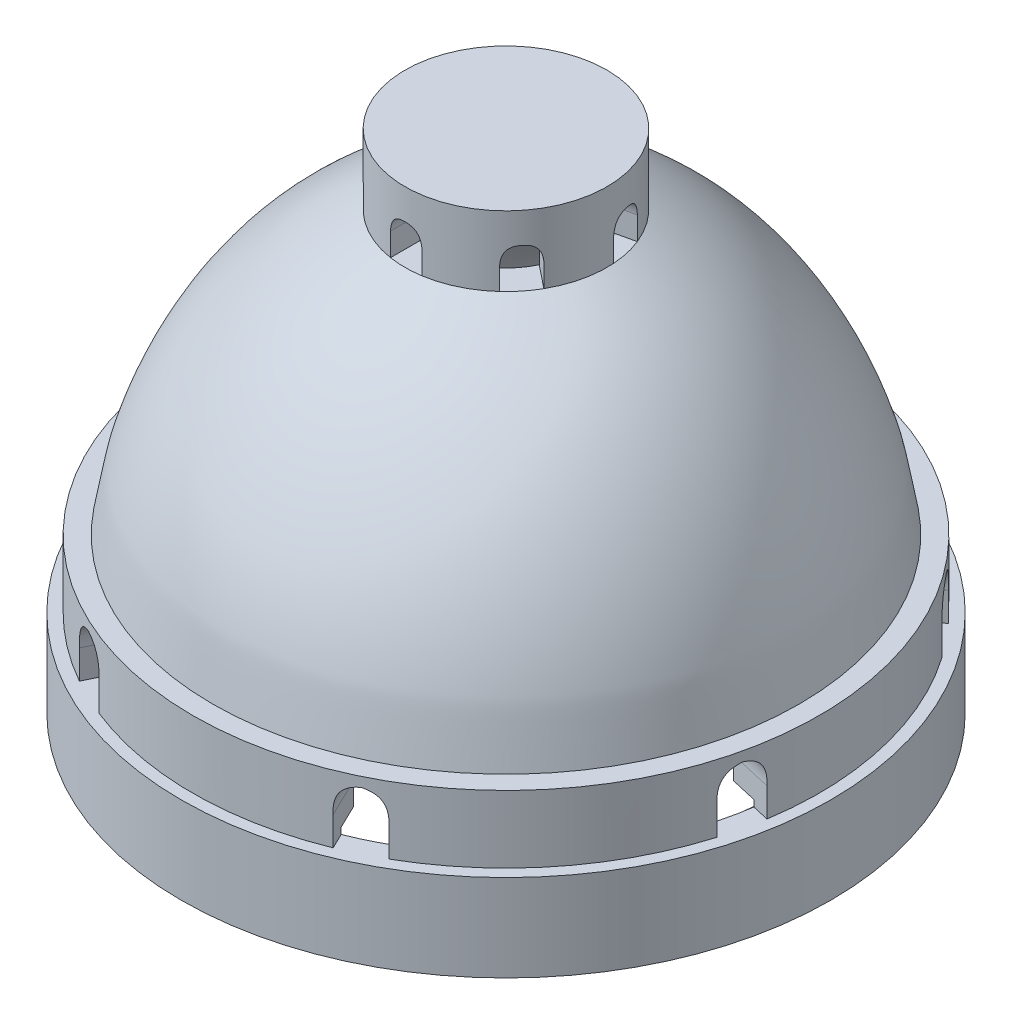
SolidWorks part; units mm, degrees
ref_plane "Front Plane" through (0, 0, 0) normal (0, 0, 1) x (1, 0, 0)
ref_plane "Top Plane" through (0, 0, 0) normal (0, 1, 0) x (1, 0, 0)
ref_plane "Right Plane" through (0, 0, 0) normal (1, 0, 0) x (0, 0, -1)
sketch "Szkic2" plane through (0, 0, 0) normal (0, 0, 1) x (1, 0, 0)
  line L12 (11.25, 0) -> (11.25, 3.0128)
  line L13 (11.25, 3.0128) -> (10.85, 3.0128)
  line L14 (10.85, 3.0128) -> (10.85, 5.3434)
  line L15 (10.85, 5.3434) -> (10.1612, 5.3434)
  line L20 (-1, 14.0477) -> (-1, -1) construction
  line L21 (-1, -1) -> (11.25, -1) construction
  line L22 (-1, 17.536) -> (-1, 14.0477) construction
  line L23 (0, 16.536) -> (0, 17.536)
  line L24 (10.25, 0) -> (11.25, 0)
  line L25 (9.3227, 4.3434) -> (9.3227, 3.2366)
  line L26 (11.25, -1) -> (11.25, 3.0128) construction
  line L27 (3.5, 17.536) -> (-1, 17.536) construction
  line L28 (0, 0) -> (10.25, 0) construction
  line L29 (0, 14.0477) -> (0, 0) construction
  line L30 (0, 16.536) -> (0, 14.0477) construction
  line L31 (9.85, 4.3434) -> (9.3227, 4.3434) construction
  line L32 (9.85, 2.0128) -> (9.85, 4.3434) construction
  line L34 (10.25, 0) -> (10.25, 2.0128) construction
  line L35 (10.25, 2.0128) -> (9.85, 2.0128) construction
  line L40 (10.25, 2) -> (10.25, 0)
  line L41 (3.5, 17.536) -> (3.5, 15.1137)
  line L42 (3.5, 15.1137) -> (3.5, 17.536) construction
  line L43 (2.5, 16.536) -> (2.5, 14.4857)
  line L44 (2.5, 16.536) -> (0, 16.536)
  line L45 (2.5, 14.4857) -> (2.5, 16.536) construction
  line L46 (2.5, 16.536) -> (0, 16.536) construction
  line L47 (0, 17.536) -> (3.5, 17.536)
  line L48 (9.3227, 3.2366) -> (10.25, 3.2366)
  line L49 (10.25, 3.2366) -> (10.25, 2)
  spline S0 degree 3 poles (2.5, 14.4857) (4.3578, 13.6298) (7.6202, 10.9724) (8.8036, 7.1397) (8.8862, 6.8132) (9.3227, 4.3434) knots 0 0 0 0 0.216018 0.669741 0.815583 0.815583 0.815583 0.815583
  spline S1 degree 1 poles (3.5, 15.1137) (10.1612, 5.3434) knots 0 0 1 1 construction
  spline S2 degree 3 poles (10.1612, 5.3434) (10.1354, 5.4883) (10.0804, 5.7971) (9.9968, 6.2632) (9.9178, 6.6947) (9.8566, 7.0096) (9.8107, 7.2181) (9.7666, 7.3767) (9.7217, 7.5269) (9.6353, 7.8101) (9.4948, 8.226) (9.2471, 8.8839) (8.8154, 9.8582) (8.0585, 11.1768) (7.1976, 12.3116) (6.338, 13.2005) (5.567, 13.8577) (4.7945, 14.3908) (4.092, 14.8047) (3.6956, 15.015) (3.5, 15.1137) knots 0.022269 0.022269 0.022269 0.022269 0.034378 0.046486 0.070703 0.094919 0.119136 0.143352 0.167569 0.216002 0.264435 0.312869 0.409735 0.506602 0.603468 0.651901 0.700334 0.748768 0.772984 0.797201 0.797201 0.797201 0.797201
  dimension "D1" = 1
  dimension "D5" = 1
revolve "Obrót1" add sketch "Szkic2" angle 360 about L23
sketch "Szkic3" plane through (0, 0, 0) normal (0, 0, 1) x (1, 0, 0)
  line L1 (0.6993, 3.0128) -> (-0.7501, 3.0128)
  line L2 (0.6993, 3.0128) -> (0.6993, 4.0128)
  line L3 (11.25, 3.0128) -> (-11.25, 3.0128) construction
  line L5 (-0.7501, 3.0128) -> (-0.7501, 4.0128)
  spline S0 degree 2 poles (0.6993, 4.0128) (0.7426, 4.9039) (-0.0254, 5.0128) knots 0 0 0 1 1 1
  spline S1 degree 2 poles (-0.7501, 4.0128) (-0.7934, 4.9039) (-0.0254, 5.0128) knots 0 0 0 1 1 1
  point P13 (0, 4.0128)
  dimension "D1" = 1
  dimension "D2" = 1
  dimension "D3" = 1
  dimension "D4" = 1
extrude "Wytnij-wyciągnięcie1" cut sketch "Szkic3" against normal blind 12
ref_axis "Oś1" through (0, 17.536, 0) along (0, -1, 0)
pattern_circular "Szyk kołowy1" count 7 over 360 about axis through (0, 17.536, 0) along (0, -1, 0) of "Wytnij-wyciągnięcie1"
sketch "Szkic4" plane through (0, 0, 0) normal (0, 0, 1) x (1, 0, 0)
  line L1 (3.5, 15.1137) -> (-3.5, 15.1137) construction
  line L2 (0.5448, 15.1137) -> (0.5448, 15.9137)
  line L3 (3.5, 17.536) -> (-3.5, 17.536) construction
  line L6 (-0.5448, 15.1137) -> (-0.5448, 15.9137)
  line L7 (-0.5448, 15.1137) -> (0.5448, 15.1137)
  spline S0 degree 2 poles (0.5448, 15.9137) (0.5086, 16.4857) (0, 16.486) knots 0 0 0 1 1 1
  spline S1 degree 2 poles (-0.5448, 15.9137) (-0.5086, 16.4857) (0, 16.486) knots 0 0 0 1 1 1
  dimension "D1" = 1.05
  dimension "D2" = 0.8
extrude "Wytnij-wyciągnięcie2" cut sketch "Szkic4" along normal blind 5
pattern_circular "Szyk kołowy2" count 7 over 360 about axis through (0, 17.536, 0) along (0, -1, 0) of "Wytnij-wyciągnięcie2"
thread "Gwint1" pitch 1 method extrude profile "Profil gwintu1" start angle 0, offset 0, length 2, pitch 1, diameter 20.5
ref_plane "Płaszczyzna1" through (10.25, 0, 0) normal (0, 0, 1) x (1, 0, 0)
sketch "Profil gwintu1" plane through (10.25, 0, 0) normal (0, 0, 1) x (1, 0, 0)
  line L0 (0, 0) -> (0, 1) construction
  line L11 (0, 0) -> (0, 0.875)
  line L12 (0, 0.875) -> (-0.5413, 0.5625)
  line L13 (-0.5413, 0.5625) -> (-0.5413, 0.3125)
  line L15 (-0.5413, 0.3125) -> (0, 0)
  line L17 (-0.5413, 0.4375) -> (0, 0.4375) construction
  point P2 (0, 0)
  dimension "Pitch" = 1
  dimension "Profile_Angle" = 60
  dimension "Profile_Land" = 0.25
  dimension "Profile_Height" = 0.5413
